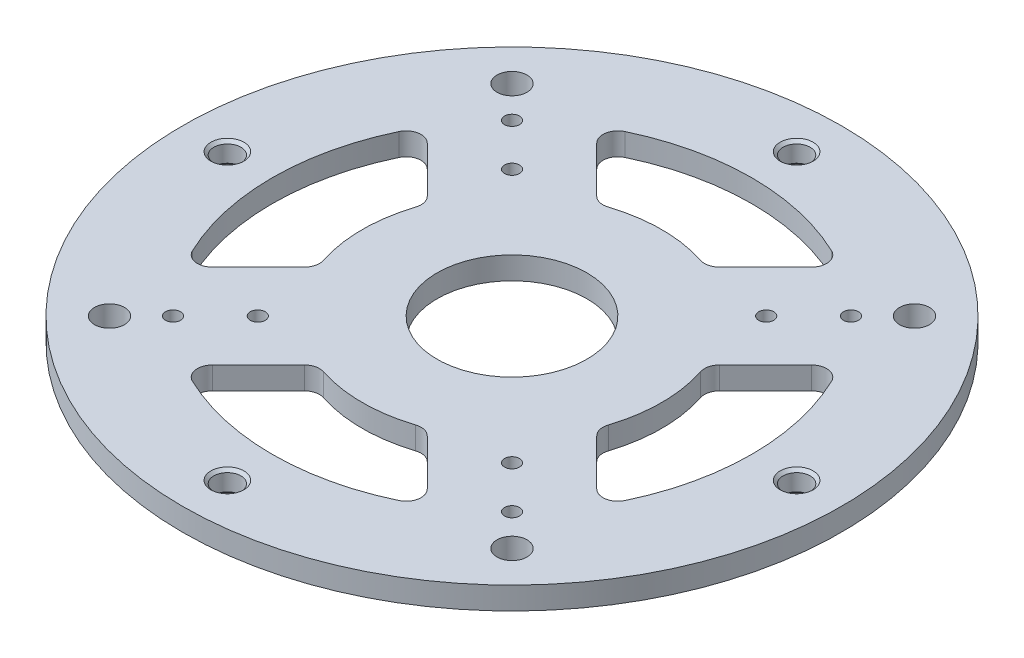
SolidWorks part; units mm, degrees
material "6061-T4 (SS)"
ref_plane "Front Plane" through (0, 0, 0) normal (0, 0, 1) x (1, 0, 0)
ref_plane "Top Plane" through (0, 0, 0) normal (0, 1, 0) x (1, 0, 0)
ref_plane "Right Plane" through (0, 0, 0) normal (1, 0, 0) x (0, 0, -1)
sketch "Sketch2" plane through (0, 0, 0) normal (0, 1, 0) x (1, 0, 0)
  line L0 (0, 0) -> (0, 114.3) construction
  line L3 (22.4506, 22.4506) -> (98.7828, 98.7828) construction
  line L4 (61.9546, 26.0336) -> (81.4605, 45.5395)
  line L5 (26.0336, 61.9546) -> (45.5395, 81.4605)
  line L7 (61.9546, -26.0336) -> (81.4605, -45.5395)
  line L8 (4.4901, 40.4112) -> (80.8223, 116.7433) construction
  line L9 (40.4112, 4.4901) -> (116.7433, 80.8223) construction
  line L10 (26.0336, -61.9546) -> (45.5395, -81.4605)
  line L11 (-26.0336, -61.9546) -> (-45.5395, -81.4605)
  line L12 (-61.9546, -26.0336) -> (-81.4605, -45.5395)
  line L13 (-61.9546, 26.0336) -> (-81.4605, 45.5395)
  line L14 (-26.0336, 61.9546) -> (-45.5395, 81.4605)
  arc A0 (-91.6807, 43.786) -> (-91.6807, -43.786) centre (0, 0) ccw
  circle A1 centre (0, 0) radius 139.7
  arc A2 (43.786, 91.6807) -> (-43.786, 91.6807) centre (0, 0) ccw
  arc A3 (91.6807, -43.786) -> (91.6807, 43.786) centre (0, 0) ccw
  arc A4 (-43.786, -91.6807) -> (43.786, -91.6807) centre (0, 0) ccw
  arc A5 (-19.585, -60.4043) -> (19.585, -60.4043) centre (0, 0) ccw
  arc A6 (-81.4605, 45.5395) -> (-91.6807, 43.786) centre (-85.9506, 41.0494) ccw
  arc A7 (-91.6807, -43.786) -> (-81.4605, -45.5395) centre (-85.9506, -41.0494) ccw
  arc A8 (-45.5395, -81.4605) -> (-43.786, -91.6807) centre (-41.0494, -85.9506) ccw
  arc A9 (43.786, -91.6807) -> (45.5395, -81.4605) centre (41.0494, -85.9506) ccw
  arc A10 (60.4043, -19.585) -> (60.4043, 19.585) centre (0, 0) ccw
  arc A11 (19.585, 60.4043) -> (-19.585, 60.4043) centre (0, 0) ccw
  arc A12 (81.4605, -45.5395) -> (91.6807, -43.786) centre (85.9506, -41.0494) ccw
  arc A13 (91.6807, 43.786) -> (81.4605, 45.5395) centre (85.9506, 41.0494) ccw
  arc A14 (-60.4043, -19.585) -> (-61.9546, -26.0336) centre (-66.4447, -21.5435) cw
  arc A15 (45.5395, 81.4605) -> (43.786, 91.6807) centre (41.0494, 85.9506) ccw
  arc A16 (-43.786, 91.6807) -> (-45.5395, 81.4605) centre (-41.0494, 85.9506) ccw
  arc A17 (-60.4043, 19.585) -> (-60.4043, -19.585) centre (0, 0) ccw
  circle A18 centre (0, 0) radius 31.75
  arc A19 (-26.0336, -61.9546) -> (-19.585, -60.4043) centre (-21.5435, -66.4447) cw
  arc A20 (19.585, -60.4043) -> (26.0336, -61.9546) centre (21.5435, -66.4447) cw
  arc A21 (61.9546, -26.0336) -> (60.4043, -19.585) centre (66.4447, -21.5435) cw
  arc A22 (60.4043, 19.585) -> (61.9546, 26.0336) centre (66.4447, 21.5435) cw
  arc A23 (26.0336, 61.9546) -> (19.585, 60.4043) centre (21.5435, 66.4447) cw
  arc A24 (-19.585, 60.4043) -> (-26.0336, 61.9546) centre (-21.5435, 66.4447) cw
  arc A25 (-61.9546, 26.0336) -> (-60.4043, 19.585) centre (-66.4447, 21.5435) cw
  point P28 (-51.6003, -87.5213)
  point P29 (0, 0)
  point P39 (87.5213, -51.6003)
  point P43 (-23.1922, -59.1132)
  point P47 (51.6003, 87.5213)
  point P52 (23.1922, -59.1132)
  point P55 (59.1132, -23.1922)
  point P58 (59.1132, 23.1922)
  point P61 (23.1922, 59.1132)
  dimension "D2" = 279.4
  dimension "D5" = 127
  dimension "D4" = 203.2
  dimension "D9" = 63.5
  dimension "D10" = 6.35
  dimension "D13" = 6.35
  dimension "D3" = 45
  dimension "D8" = 50.8
  dimension "D11" = 66.4447
  dimension "D12" = 66.4447
  dimension "D6" = 25.4
  dimension "D7" = 4
extrude "Boss-Extrude1" add sketch "Sketch2" along normal blind 9.525
sketch "Sketch3" plane through (0, 9.525, 0) normal (0, 1, 0) x (1, 0, 0)
  line L0 (0, 0) -> (0, 120.65) construction
  line L1 (0, 0) -> (85.3124, 85.3124) construction
  line L2 (85.3124, 85.3124) -> (103.2729, 103.2729) construction
  line L3 (0, 0) -> (-53.8815, 53.8815) construction
  line L4 (-53.8815, 53.8815) -> (-71.842, 71.842) construction
  circle A0 centre (-71.842, 71.842) radius 3.175
  circle A1 centre (0, 0) radius 120.65 construction
  circle A2 centre (0, 120.65) radius 7.1437
  circle A3 centre (120.65, 0) radius 7.1438
  circle A4 centre (0, -120.65) radius 7.1437
  circle A5 centre (-120.65, 0) radius 7.1438
  circle A6 centre (0, 0) radius 120.65 construction
  circle A10 centre (0, 0) radius 139.7 construction
  circle A17 centre (-53.8815, 53.8815) radius 3.175
  circle A18 centre (-71.842, -71.842) radius 3.175
  circle A19 centre (71.842, -71.842) radius 3.175
  circle A20 centre (71.842, 71.842) radius 3.175
  circle A21 centre (53.8815, 53.8815) radius 3.175
  circle A22 centre (53.8815, -53.8815) radius 3.175
  circle A23 centre (-53.8815, -53.8815) radius 3.175
  circle A24 centre (85.3124, 85.3124) radius 6.35
  circle A25 centre (85.3124, -85.3124) radius 6.35
  circle A26 centre (-85.3124, -85.3124) radius 6.35
  circle A27 centre (-85.3124, 85.3124) radius 6.35
  point P17 (0, 0)
  point P26 (0, 0)
  point P39 (0, 0)
  point P47 (0, 0)
  point P54 (0, 0)
  point P63 (0, 0)
  dimension "D2" = 14.2875
  dimension "D5" = 120.65
  dimension "D6" = 76.2
  dimension "D7" = 241.3
  dimension "D9" = 25.4
  dimension "D13" = 12.7
  dimension "D14" = 45
  dimension "D15" = 4
  dimension "D4" = 45
  dimension "D3" = 4
  dimension "D11" = 4
  dimension "D12" = 4
extrude "Cut-Extrude2" cut sketch "Sketch3" against normal through all contours A24 | A25 | A26 | A27 | A0 | A17 | A20 | A21 | A19 | A22 | A18 | A23
sketch "Sketch4" plane through (0, 9.525, 0) normal (0, 1, 0) x (1, 0, 0)
  line L1 (-152.4, -152.4) -> (152.4, -152.4) construction
  line L2 (-152.4, -152.4) -> (-152.4, 152.4) construction
  line L3 (-152.4, 152.4) -> (152.4, 152.4) construction
  line L4 (152.4, -152.4) -> (152.4, 152.4) construction
  line L5 (-152.4, -152.4) -> (152.4, 152.4) construction
  line L6 (-152.4, 152.4) -> (152.4, -152.4) construction
  point P0 (0, 0)
  dimension "D1" = 304.8
sketch "Sketch5" plane through (0, 9.525, 0) normal (0, 1, 0) x (1, 0, 0)
  circle A1 centre (0, 0) radius 139.7
  circle A2 centre (0, 0) radius 139.7
  circle A3 centre (0, -120.65) radius 7.1437
  circle A4 centre (0, -120.65) radius 7.1437
  circle A5 centre (120.65, 0) radius 7.1438
  circle A6 centre (120.65, 0) radius 7.1438
  circle A7 centre (0, 120.65) radius 7.1437
  circle A8 centre (0, 120.65) radius 7.1437
  circle A9 centre (-71.842, 71.842) radius 3.175
  circle A10 centre (-71.842, 71.842) radius 3.175
  circle A11 centre (85.3124, 85.3124) radius 6.35
  circle A12 centre (85.3124, 85.3124) radius 6.35
  circle A13 centre (-53.8815, 53.8815) radius 3.175
  circle A14 centre (-53.8815, 53.8815) radius 3.175
  circle A15 centre (-120.65, 0) radius 7.1438
  circle A16 centre (-120.65, 0) radius 7.1438
  circle A17 centre (71.842, 71.842) radius 3.175
  circle A18 centre (71.842, 71.842) radius 3.175
  circle A19 centre (71.842, -71.842) radius 3.175
  circle A20 centre (71.842, -71.842) radius 3.175
  circle A21 centre (-71.842, -71.842) radius 3.175
  circle A22 centre (-71.842, -71.842) radius 3.175
  circle A23 centre (-85.3124, 85.3124) radius 6.35
  circle A24 centre (-85.3124, 85.3124) radius 6.35
  circle A25 centre (-85.3124, -85.3124) radius 6.35
  circle A26 centre (-85.3124, -85.3124) radius 6.35
  circle A27 centre (85.3124, -85.3124) radius 6.35
  circle A28 centre (85.3124, -85.3124) radius 6.35
  circle A29 centre (-53.8815, -53.8815) radius 3.175
  circle A30 centre (-53.8815, -53.8815) radius 3.175
  circle A31 centre (53.8815, -53.8815) radius 3.175
  circle A32 centre (53.8815, -53.8815) radius 3.175
  circle A33 centre (53.8815, 53.8815) radius 3.175
  circle A34 centre (53.8815, 53.8815) radius 3.175
  dimension "D1" = 0
  dimension "D2" = 0
  dimension "D3" = 0
  dimension "D4" = 0
  dimension "D5" = 0
  dimension "D6" = 0
  dimension "D7" = 0
  dimension "D8" = 0
  dimension "D9" = 0
  dimension "D10" = 0
  dimension "D11" = 0
  dimension "D12" = 0
  dimension "D13" = 0
  dimension "D14" = 0
  dimension "D15" = 0
  dimension "D16" = 0
  dimension "D17" = 0
hole_wizard "1/2-20 Tapped Hole1" positions "Sketch6" profile "Sketch7" tap size "1/2-20" standard "ANSI Inch" end condition through all
sketch "Sketch6" plane through (0, 9.525, 0) normal (0, 1, 0) x (1, 0, 0)
  point P0 (-120.65, 0)
  point P3 (0, 120.65)
  point P6 (120.65, 0)
  point P9 (0, -120.65)
sketch "Sketch7" plane through (-120.65, 9.525, 0) normal (1, 0, 0) x (0, 0, 1)
  line L0 (0, 0) -> (0, 9.525)
  line L1 (0, 9.525) -> (6.985, 9.525)
  line L2 (5.7544, 8.2944) -> (5.7544, 1.2306)
  line L3 (5.7544, 1.2306) -> (6.985, 0)
  line L5 (6.985, 0) -> (0, 0)
  line L6 (-5.7544, 1.2306) -> (-6.985, 0) construction
  line L7 (6.985, 9.525) -> (5.7544, 8.2944)
  line L8 (-6.985, 9.525) -> (-5.7544, 8.2944) construction
  line L11 (0, -6.35) -> (0, 107.95) construction
  dimension "Thru Tap Drill Dia." = 11.5087
  dimension "Thru Tap Drill Depth" = 9.525
  dimension "Near C'Sink Dia." = 13.97
  dimension "Near C'Sink Angle" = 90
  dimension "Far C'Sink Dia." = 13.97
  dimension "Far C'Sink Angle" = 90
cosmetic thread "Hole Thread1" parameters "D2"=12.7
cosmetic thread "Hole Thread2" parameters "D2"=12.7
cosmetic thread "Hole Thread3" parameters "D2"=12.7
cosmetic thread "Hole Thread4" parameters "D2"=12.7
